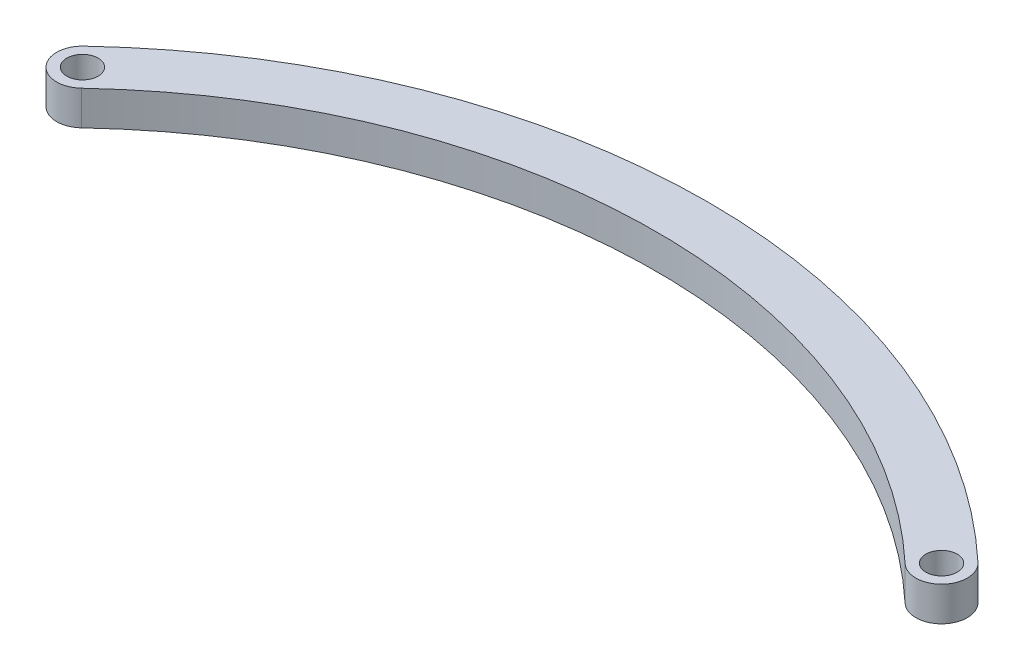
SolidWorks part; units mm, degrees
ref_plane "Front Plane" through (0, 0, 0) normal (0, 0, 1) x (1, 0, 0)
ref_plane "Top Plane" through (0, 0, 0) normal (0, 1, 0) x (1, 0, 0)
ref_plane "Right Plane" through (0, 0, 0) normal (1, 0, 0) x (0, 0, -1)
sketch "Esquisse1" plane through (0, 0, 0) normal (0, 1, 0) x (1, 0, 0)
  line L0 (-50, 0) -> (0, 0) construction
  line L1 (0, 0) -> (50, 0) construction
  circle A0 centre (-50, 0) radius 1.825
  circle A1 centre (50, 0) radius 1.825
  circle A2 centre (-50, 0) radius 3
  circle A3 centre (50, 0) radius 3
  circle A4 centre (0, -53.1883) radius 70
  circle A5 centre (0, -53.1883) radius 76
  dimension "D2" = 3.65
  dimension "D3" = 6
  dimension "D4" = 140
  dimension "D5" = 152
  dimension "D1" = 50
extrude "Boss.-Extru.1" add sketch "Esquisse1" along normal blind 4 contours A3 A5 A2 A4 | A2 A0 | A3 A1 region at (-47.3243, 0, 1.157) region at (-48.3843, 0, -3.7363) region at (52.6757, 0, -1.157)
